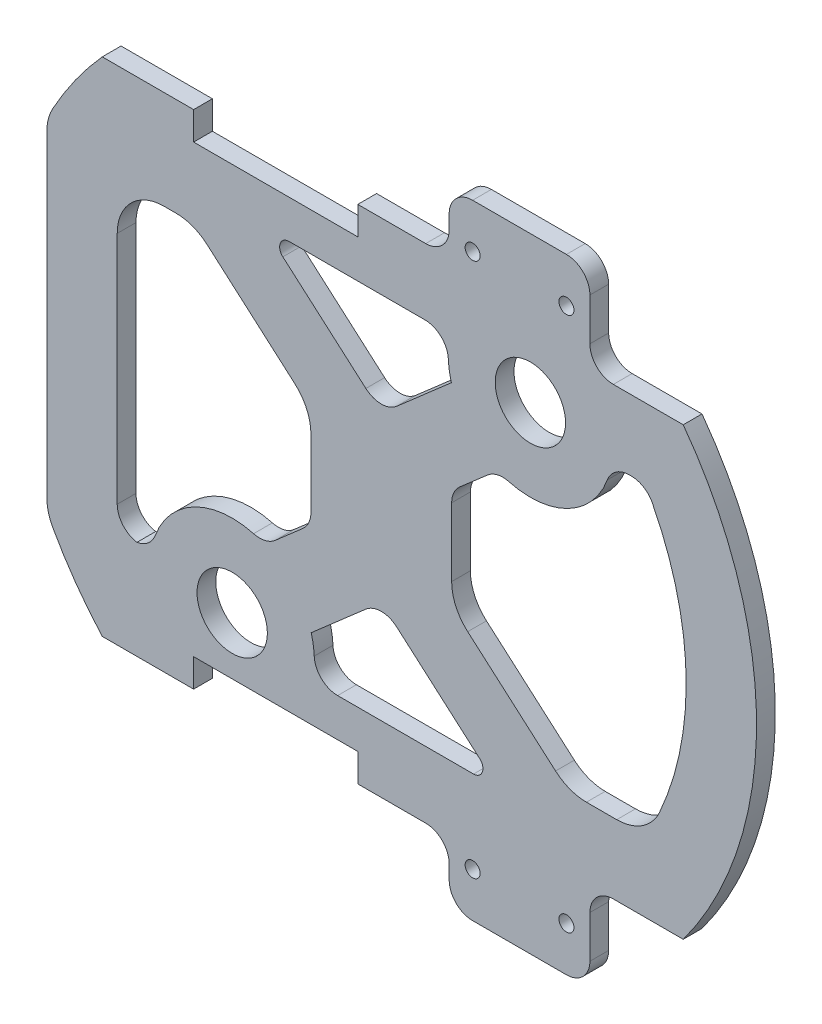
SolidWorks part; units mm, degrees
material "Acrílico (médio-alto impacto)"
ref_plane "Plano frontal" through (0, 0, 0) normal (0, 0, 1) x (1, 0, 0)
ref_plane "Plano superior" through (0, 0, 0) normal (0, 1, 0) x (1, 0, 0)
ref_plane "Plano direito" through (0, 0, 0) normal (1, 0, 0) x (0, 0, -1)
sketch "Esboço1" plane through (0, 0, 0) normal (0, 0, 1) x (1, 0, 0)
  line L0 (80, 0) -> (0, 0) construction
  line L1 (-80, -66.5) -> (80, -66.5)
  line L2 (-80, -66.5) -> (-80, 66.5)
  line L3 (-80, 66.5) -> (80, 66.5)
  line L4 (80, -66.5) -> (80, 66.5)
  line L5 (-80, -66.5) -> (80, 66.5) construction
  line L6 (-80, 66.5) -> (80, -66.5) construction
  line L7 (80, 47.5) -> (-80, 47.5) construction
  line L8 (80, -47.5) -> (-80, -47.5) construction
  line L9 (14.4719, 66.5) -> (14.4719, 53.5)
  line L10 (0, 0) -> (0, 66.5) construction
  line L11 (44.4719, 66.5) -> (44.4719, 47.5)
  line L12 (-5.0035, -47.5) -> (-40.0035, -47.5)
  line L13 (14.4719, -66.5) -> (14.4719, -53.5)
  line L14 (44.4719, 47.5) -> (64.372, 47.5)
  line L15 (28.6277, 47.5) -> (28.6277, 66.5) construction
  line L16 (14.4719, 53.5) -> (-59.479, 53.5)
  line L17 (-40.0035, -53.5) -> (-40.0035, -47.5)
  line L18 (-31.7837, -35.2994) -> (31.7837, 35.2994) construction
  line L24 (-56.2917, 32.5) -> (-39.9802, 32.5)
  line L25 (-39.9802, 32.5) -> (-15, 10.6848)
  line L30 (-15, 10.6848) -> (-15, -10.6848)
  line L31 (-39.9802, -32.5) -> (-15, -10.6848)
  line L36 (-56.2917, -32.5) -> (-39.9802, -32.5)
  line L37 (56.2917, 32.5) -> (39.9802, 32.5)
  line L57 (39.9802, 32.5) -> (15, 10.6848)
  line L58 (15, 10.6848) -> (15, -10.6848)
  line L59 (39.9802, -32.5) -> (15, -10.6848)
  line L60 (56.2917, -32.5) -> (39.9802, -32.5)
  line L61 (-25, -39.3325) -> (0, -17.5)
  line L63 (-25, -39.3325) -> (25, -39.3325)
  line L64 (25, -39.3325) -> (0, -17.5)
  line L65 (-25, 39.3325) -> (0, 17.5)
  line L66 (25, 39.3325) -> (0, 17.5)
  line L67 (-25, 39.3325) -> (25, 39.3325)
  line L69 (-5.0035, -53.5) -> (-40.0035, -53.5)
  line L70 (-5.0035, 53.5) -> (-40.0035, 53.5)
  line L71 (-5.0035, 53.5) -> (-5.0035, 47.5)
  line L72 (-5.0035, 47.5) -> (-40.0035, 47.5)
  line L73 (-40.0035, 53.5) -> (-40.0035, 47.5)
  line L74 (-5.0035, 53.5) -> (-40.0035, 47.5) construction
  line L75 (-5.0035, 47.5) -> (-40.0035, 53.5) construction
  line L76 (-5.0035, -53.5) -> (-5.0035, -47.5)
  line L77 (14.4719, -53.5) -> (-59.479, -53.5)
  line L78 (44.4719, -66.5) -> (44.4719, -47.5)
  line L79 (44.4719, -47.5) -> (64.372, -47.5)
  line L80 (-71.2917, -36.2974) -> (-71.2917, 36.2974)
  line L81 (-56.2917, 32.5) -> (-56.2917, -32.5)
  circle A0 centre (0, 0) radius 80
  circle A1 centre (-31.7837, -35.2994) radius 7.5
  circle A2 centre (31.7837, 35.2994) radius 7.5
  circle A3 centre (19.4719, 57) radius 1.6
  circle A8 centre (19.4719, -57) radius 1.6
  arc A9 (-56.2917, -32.5) -> (-56.2917, 32.5) centre (0, 0) cw
  arc A11 (56.2917, -32.5) -> (56.2917, 32.5) centre (0, 0) ccw
  circle A12 centre (-31.7837, -35.2994) radius 17.5
  circle A13 centre (31.7837, 35.2994) radius 17.5
  circle A14 centre (39.4719, 57) radius 1.6
  circle A15 centre (39.4719, -57) radius 1.6
  point P0 (0, 0)
  point P37 (-22.5035, 50.5)
  point P38 (28.6277, 57)
  point P45 (-65, 0)
  point P65 (-22.5035, 53.5)
  dimension "D6" = 15
  dimension "D7" = 3.2
  dimension "D18" = 15
  dimension "D9" = 15
  dimension "D11" = 35
  dimension "D1" = 95
  dimension "D2" = 19
  dimension "D3" = 160
  dimension "D4" = 95
  dimension "D5" = 48
  dimension "D8" = 15
  dimension "D10" = 30
  dimension "D12" = 30
  dimension "D13" = 35
  dimension "D14" = 5
  dimension "D15" = 50
  dimension "D16" = 5
  dimension "D17" = 6
  dimension "D19" = 35
  dimension "D21" = 15
extrude "Ressalto-extrusão1" add sketch "Esboço1" along normal blind 4 contours A0 L13 L1 L12 L17 L3 L9 A13 L37 A11 L60 L59 L58 L57 A12 L36 A9 L24 L25 L30 L31 A3 A14 A8 | L37 A13 L57 A2 | L57 A13 L37 | L67 A13 L66 | L61 A12 L31 A1 L36 L13 L63 | L31 A12 L36 | L63 A12 L61 | A9 L81 region at (6.2474, -0.5263, 0) region at (-47.0413, -42.87, 0) region at (-38.1575, -24.9182, 0) region at (-17.9859, -36.3042, 0) region at (-59.7958, 0, 0) region at (38.1575, 24.9182, 0) region at (44.5193, 32.9814, 0) region at (17.9859, 36.3042, 0)
fillet "Filete2" radius 10 8 edges at (56.2917, -32.5, 2) (39.9802, -32.5, 2) (15, -10.6848, 2) (-15, 10.6848, 2) (-39.9802, 32.5, 2) (-71.2917, -36.2974, 2) (-71.2917, 36.2974, 2) (-56.2917, 32.5, 2)
fillet "Filete3" radius 5 20 edges at (56.2917, 32.5, 2) (49.0584, 32.5, 2) (24.8078, 19.2499, 2) (15, 10.6848, 2) (-15, -10.6848, 2) (-24.8078, -19.2499, 2) (-49.0584, -32.5, 2) (14.7548, 39.3325, 2) (0, 17.5, 2) (0, -17.5, 2) (-14.7548, -39.3325, 2) (14.4719, 53.5, 2) (14.4719, -53.5, 2) (44.4719, -47.5, 2) (44.4719, 47.5, 2) (14.4719, -66.5, 2) (14.4719, 66.5, 2) (44.4719, 66.5, 2) (44.4719, -66.5, 2) (-56.2917, -32.5, 2)
fillet "Filete4" radius 2 2 edges at (25, -39.3325, 2) (-25, 39.3325, 2)
